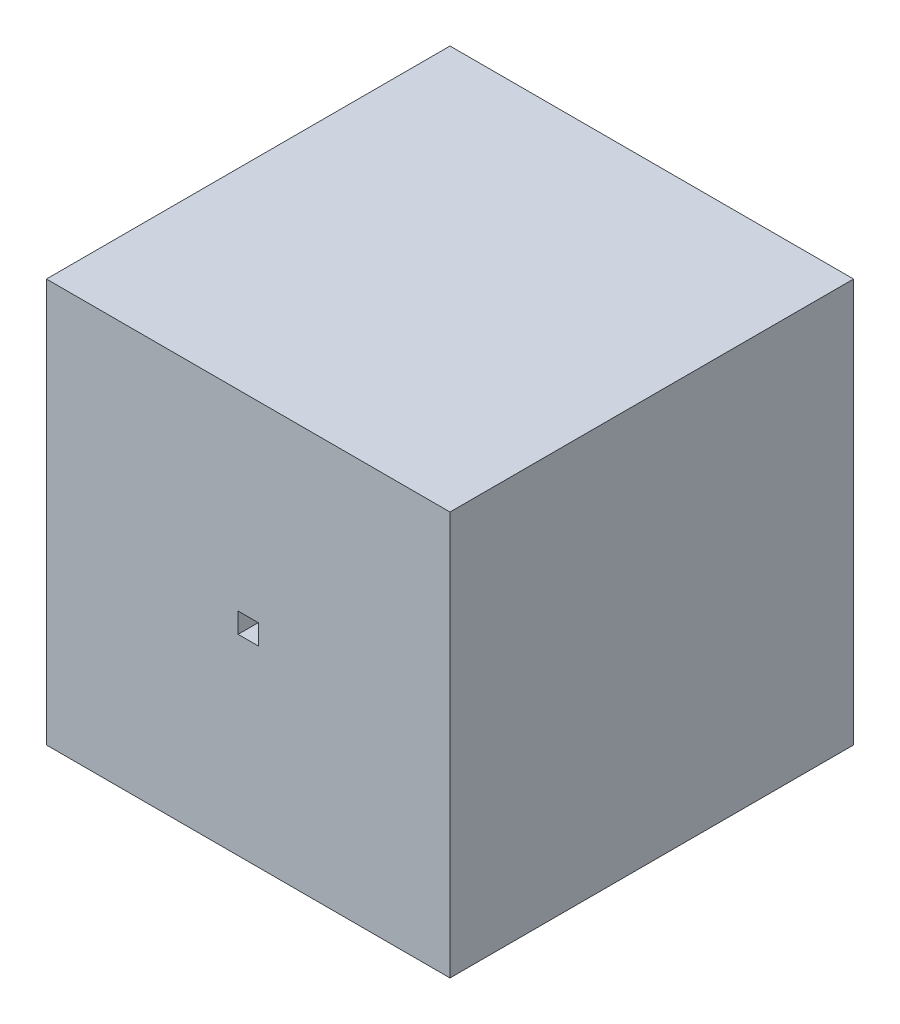
SolidWorks part; units mm, degrees
ref_plane "Alzado" through (0, 0, 0) normal (0, 0, 1) x (1, 0, 0)
ref_plane "Planta" through (0, 0, 0) normal (0, 1, 0) x (1, 0, 0)
ref_plane "Vista lateral" through (0, 0, 0) normal (1, 0, 0) x (0, 0, -1)
sketch "Croquis1" plane through (0, 0, 0) normal (0, 0, 1) x (1, 0, 0)
  line L1 (-50, -50) -> (50, -50)
  line L2 (-50, -50) -> (-50, 50)
  line L3 (-50, 50) -> (50, 50)
  line L4 (50, -50) -> (50, 50)
  line L5 (-50, -50) -> (50, 50) construction
  line L6 (-50, 50) -> (50, -50) construction
  point P0 (0, 0)
  dimension "D1" = 100
  dimension "D2" = 100
extrude "Saliente-Extruir1" add sketch "Croquis1" along normal blind 100
sketch "Croquis2" plane through (0, 0, 0) normal (0, 0, -1) x (-1, 0, 0)
  line L1 (-2.5, 2.5) -> (2.5, 2.5)
  line L2 (-2.5, 2.5) -> (-2.5, -2.5)
  line L3 (-2.5, -2.5) -> (2.5, -2.5)
  line L4 (2.5, 2.5) -> (2.5, -2.5)
  line L5 (-2.5, 2.5) -> (2.5, -2.5) construction
  line L6 (-2.5, -2.5) -> (2.5, 2.5) construction
  point P0 (0, 0)
  dimension "D1" = 5
  dimension "D2" = 5
extrude "Cortar-Extruir1" cut sketch "Croquis2" against normal through all
